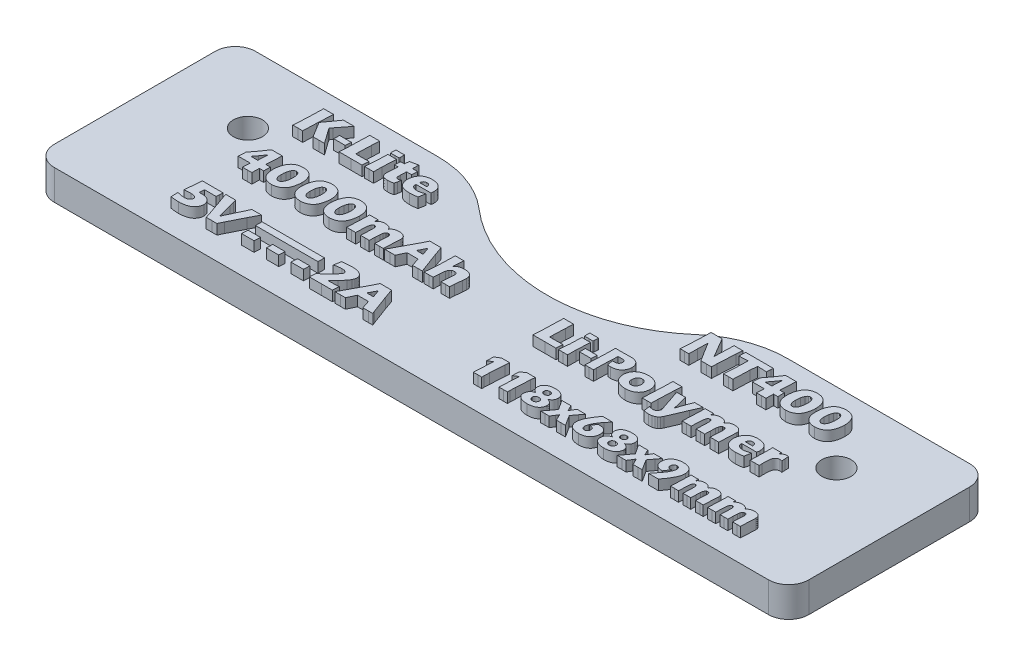
SolidWorks part; units mm, degrees
ref_plane "Front Plane" through (0, 0, 0) normal (0, 0, 1) x (1, 0, 0)
ref_plane "Top Plane" through (0, 0, 0) normal (0, 1, 0) x (1, 0, 0)
ref_plane "Right Plane" through (0, 0, 0) normal (1, 0, 0) x (0, 0, -1)
sketch "Sketch1" plane through (0, 0, 0) normal (0, 1, 0) x (1, 0, 0)
  line L1 (0, 0) -> (75, 0)
  line L2 (0, 0) -> (0, 20)
  line L3 (0, 20) -> (75, 20)
  line L4 (75, 0) -> (75, 20)
  dimension "D1" = 75
  dimension "D2" = 20
extrude "Boss-Extrude1" add sketch "Sketch1" along normal blind 3
fillet "Fillet1" radius 2 4 edges at (75, 1.5, -20) (75, 1.5, 0) (0, 1.5, 0) (0, 1.5, -20)
sketch "Sketch2" plane through (0, 3, 0) normal (0, 1, 0) x (1, 0, 0)
  line L0 (8.25, 13) -> (66.75, 13) construction
  line L3 (2, 0) -> (73, 0) construction
  line L4 (37.5, 20) -> (37.5, 0) construction
  line L5 (73, 20) -> (2, 20) construction
  circle A0 centre (8.25, 13) radius 1.45
  circle A1 centre (66.75, 13) radius 1.45
  point P8 (37.5, 13)
  dimension "D3" = 2.9
  dimension "D4" = 2.9
  dimension "D1" = 13
  dimension "D2" = 58.5
extrude "Cut-Extrude1" cut sketch "Sketch2" against normal through all
sketch "Sketch3" plane through (0, 3, 0) normal (0, 1, 0) x (1, 0, 0)
  line L0 (37.5, 20) -> (37.5, 0) construction
  line L1 (73, 20) -> (2, 20) construction
  line L2 (2, 0) -> (73, 0) construction
  circle A0 centre (37.5, 30) radius 16.5
  dimension "D1" = 33
  dimension "D2" = 10
extrude "Cut-Extrude2" cut sketch "Sketch3" against normal blind 10
fillet "Fillet2" radius 10 2 edges at (50.6244, 1.5, -20) (24.3756, 1.5, -20)
sketch "Sketch4" plane through (0, 3, 0) normal (0, 1, 0) x (1, 0, 0)
  line L0 (2, 0) -> (73, 0) construction
  line L1 (18, 4) -> (24.2137, 4)
  line L2 (18, 4) -> (18, 4.65)
  line L3 (18, 4.65) -> (24.2137, 4.65)
  line L4 (24.2137, 4) -> (24.2137, 4.65)
  line L5 (18, 4) -> (24.2137, 4.65) construction
  line L6 (18, 4.65) -> (24.2137, 4) construction
  text T0 "K-Lite                       NT400\r\n4000mAh       Li-Polymer\r\n5V       2A" font "Eras Bold ITC" height in points 12
  text T1 "118x68x9mm" font "Eras Bold ITC" height in points 10
  text T2 "- - - " font "Eras Bold ITC" height in points 12
  point P1 (0, 0)
  point P5 (0, 0)
  point P6 (0, 0)
  point P7 (0, 0)
  point P24 (21.1068, 4.325)
  dimension "D1" = 0.65
  dimension "D2" = 4
extrude "Boss-Extrude2" add sketch "Sketch4" along normal blind 1
